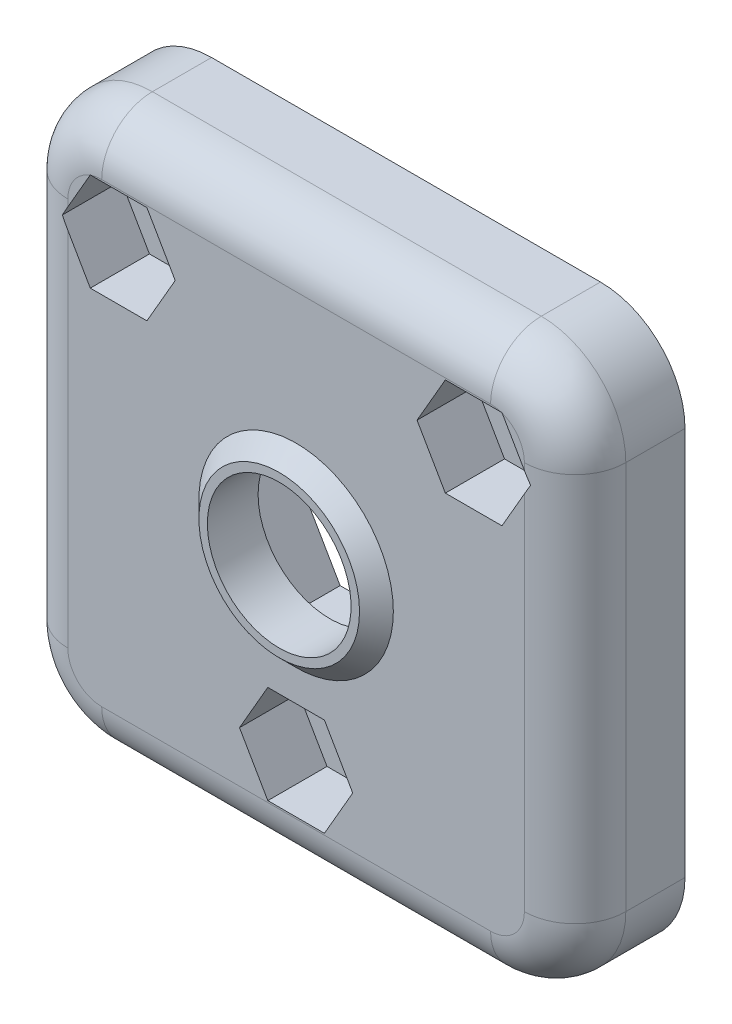
SolidWorks part; units mm, degrees
ref_plane "Plano frontal" through (0, 0, 0) normal (0, 0, 1) x (1, 0, 0)
ref_plane "Plano superior" through (0, 0, 0) normal (0, 1, 0) x (1, 0, 0)
ref_plane "Plano direito" through (0, 0, 0) normal (1, 0, 0) x (0, 0, -1)
sketch "Esboço1" plane through (0, 0, 0) normal (0, 0, 1) x (1, 0, 0)
  line L0 (0, 0) -> (0, 21) construction
  line L1 (10.5, 21) -> (-10.5, 21) construction
  line L3 (-11.5, -6) -> (11.5, -6)
  line L4 (-16.5, -1) -> (-16.5, 22)
  line L5 (-11.5, 27) -> (11.5, 27)
  line L6 (16.5, -1) -> (16.5, 22)
  line L7 (-16.5, -6) -> (16.5, 27) construction
  line L8 (-16.5, 27) -> (16.5, -6) construction
  circle A0 centre (0, 0) radius 1.75
  circle A1 centre (-10.5, 21) radius 1.75
  circle A2 centre (10.5, 21) radius 1.75
  arc A3 (11.5, -6) -> (16.5, -1) centre (11.5, -1) ccw
  arc A4 (11.5, 27) -> (16.5, 22) centre (11.5, 22) cw
  arc A5 (-16.5, 22) -> (-11.5, 27) centre (-11.5, 22) cw
  arc A6 (-11.5, -6) -> (-16.5, -1) centre (-11.5, -1) cw
  point P8 (0, 10.5)
  point P13 (0, 27)
  dimension "D1" = 3.5
  dimension "D4" = 6
  dimension "D6" = 5
  dimension "D2" = 21
  dimension "D3" = 10.5
  dimension "D5" = 6
extrude "Ressalto-extrusão1" add sketch "Esboço1" along normal blind 6.5
sketch "Esboço2" plane through (0, 0, 6.5) normal (0, 0, 1) x (1, 0, 0)
  line L1 (-12.1743, 18.1) -> (-8.8257, 18.1)
  line L2 (-8.8257, 18.1) -> (-7.1514, 21)
  line L3 (-7.1514, 21) -> (-8.8257, 23.9)
  line L4 (-8.8257, 23.9) -> (-12.1743, 23.9)
  line L5 (-12.1743, 23.9) -> (-13.8486, 21)
  line L6 (-13.8486, 21) -> (-12.1743, 18.1)
  line L7 (8.8257, 18.1) -> (12.1743, 18.1)
  line L8 (12.1743, 18.1) -> (13.8486, 21)
  line L9 (13.8486, 21) -> (12.1743, 23.9)
  line L10 (12.1743, 23.9) -> (8.8257, 23.9)
  line L11 (8.8257, 23.9) -> (7.1514, 21)
  line L12 (7.1514, 21) -> (8.8257, 18.1)
  line L13 (-1.6743, 2.9) -> (-3.3486, 0)
  line L14 (-3.3486, 0) -> (-1.6743, -2.9)
  line L15 (-1.6743, -2.9) -> (1.6743, -2.9)
  line L16 (1.6743, -2.9) -> (3.3486, 0)
  line L17 (3.3486, 0) -> (1.6743, 2.9)
  line L18 (1.6743, 2.9) -> (-1.6743, 2.9)
  circle A0 centre (-10.5, 21) radius 2.9 construction
  circle A1 centre (10.5, 21) radius 2.9 construction
  circle A2 centre (0, 0) radius 2.9 construction
  dimension "D1" = 5.8
extrude "Corte-extrusão1" cut sketch "Esboço2" against normal blind 3.5
sketch "Esboço3" plane through (0, 0, 0) normal (0, 0, -1) x (-1, 0, 0)
  line L0 (-10.5, 21) -> (10.5, 21) construction
  line L1 (0, 21) -> (0, 0) construction
  line L3 (3.8971, 17.25) -> (-3.8971, 17.25)
  line L4 (-3.8971, 17.25) -> (-7.7942, 10.5)
  line L5 (-7.7942, 10.5) -> (-3.8971, 3.75)
  line L6 (-3.8971, 3.75) -> (3.8971, 3.75)
  line L7 (3.8971, 3.75) -> (7.7942, 10.5)
  line L8 (7.7942, 10.5) -> (3.8971, 17.25)
  circle A0 centre (0, 10.5) radius 6.75 construction
  circle A1 centre (0, 10.5) radius 4.25
  dimension "D1" = 13.5
  dimension "D2" = 8.5
extrude "Corte-extrusão2" cut sketch "Esboço3" against normal blind 4.5 contours L3 L4 L5 L6 L7 L8
extrude "Corte-extrusão3" cut sketch "Esboço3<3>" against normal through all contours A1 region at (0, 10.5, 0)
sketch "Esboço3<3>" plane through (0, 0, 0) normal (0, 0, -1) x (-1, 0, 0) same geometry as "Esboço3"
sketch "Esboço4" plane through (0, 0, 6.5) normal (0, 0, 1) x (1, 0, 0)
  circle A0 centre (0, 10.5) radius 5.75
  circle A1 centre (0, 10.5) radius 4.25 construction
  circle M1 centre (0, 10.5) radius 4.25
  dimension "D1" = 1.5
extrude "Ressalto-extrusão2" add sketch "Esboço4" along normal blind 1 contours A0 M1 region at (-5.5874, 10.5, 6.5)
chamfer "Chanfro1" distance 1 angle 45 1 edges at (5.75, 10.5, 7.5)
sketch "Esboço5" plane through (0, 0, 6.5) normal (0, 0, 1) x (1, 0, 0)
  circle A0 centre (0, 10.5) radius 26.5
  circle A1 centre (0, 10.5) radius 24.5
  dimension "D1" = 53
  dimension "D2" = 2
fillet "Filete1" radius 3 8 edges at (15.0355, 25.5355, 6.5) (16.5, 10.5, 6.5) (15.0355, -4.5355, 6.5) (0, -6, 6.5) (-15.0355, -4.5355, 6.5) (-16.5, 10.5, 6.5) (-15.0355, 25.5355, 6.5) (0, 27, 6.5)
